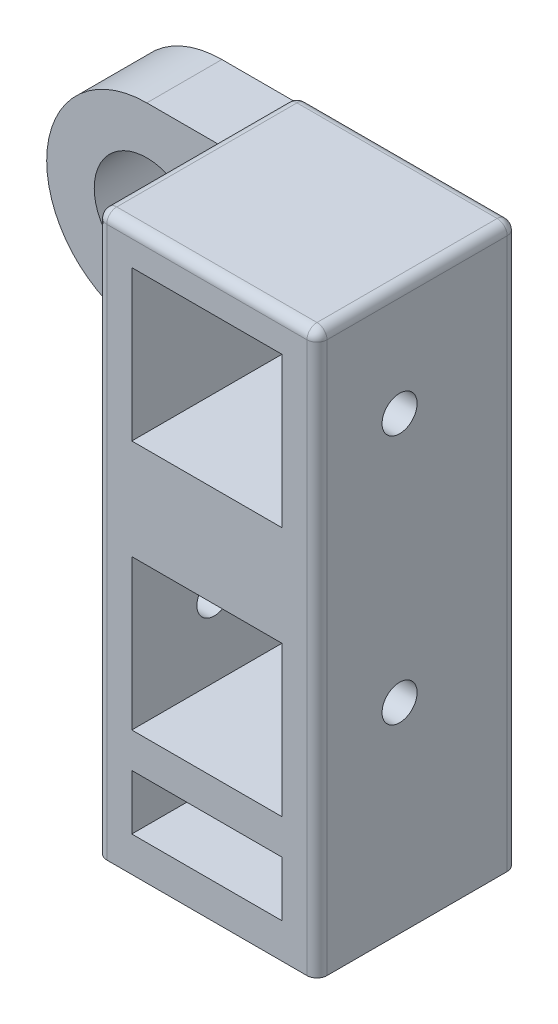
SolidWorks part; units mm, degrees
ref_plane "Front Plane" through (0, 0, 0) normal (0, 0, 1) x (1, 0, 0)
ref_plane "Top Plane" through (0, 0, 0) normal (0, 1, 0) x (1, 0, 0)
ref_plane "Right Plane" through (0, 0, 0) normal (1, 0, 0) x (0, 0, -1)
sketch "Sketch1" plane through (0, 0, 0) normal (0, 0, 1) x (1, 0, 0)
  line L1 (-25.0962, 42.3339) -> (-3.0962, 42.3339)
  line L2 (-25.0962, 42.3339) -> (-25.0962, -13.6661)
  line L3 (-25.0962, -13.6661) -> (-3.0962, -13.6661)
  line L4 (-3.0962, 42.3339) -> (-3.0962, -13.6661)
  line L5 (-21.5962, 38.8339) -> (-6.5962, 38.8339)
  line L6 (-21.5962, 38.8339) -> (-21.5962, 23.8339)
  line L7 (-21.5962, 23.8339) -> (-6.5962, 23.8339)
  line L8 (-6.5962, 38.8339) -> (-6.5962, 23.8339)
  dimension "D1" = 22
  dimension "D2" = 56
  dimension "D3" = 15
  dimension "D4" = 3.5
  dimension "D5" = 3.5
  dimension "D6" = 15
extrude "Boss-Extrude1" add sketch "Sketch1" along normal blind 20
sketch "Sketch2" plane through (0, 0, 20) normal (0, 0, 1) x (1, 0, 0)
  line L0 (-3.0962, -13.6661) -> (-3.0962, 42.3339) construction
  line L1 (-21.5962, 13.8339) -> (-6.5962, 13.8339)
  line L2 (-21.5962, 13.8339) -> (-21.5962, -1.1661)
  line L3 (-21.5962, -1.1661) -> (-6.5962, -1.1661)
  line L4 (-6.5962, 13.8339) -> (-6.5962, -1.1661)
  line L5 (-21.5962, 23.8339) -> (-6.5962, 23.8339) construction
  line L6 (-25.0962, -13.6661) -> (-3.0962, -13.6661) construction
  line L7 (-21.5962, -4.6661) -> (-6.5962, -4.6661)
  line L8 (-21.5962, -4.6661) -> (-21.5962, -10.1661)
  line L9 (-21.5962, -10.1661) -> (-6.5962, -10.1661)
  line L10 (-6.5962, -4.6661) -> (-6.5962, -10.1661)
  dimension "D1" = 15
  dimension "D2" = 3.5
  dimension "D3" = 10
  dimension "D4" = 15
  dimension "D5" = 15
  dimension "D6" = 3.5
  dimension "D7" = 3.5
extrude "Cut-Extrude1" cut sketch "Sketch2" against normal offset from surface (15.5 mm away) 4.5 up to face at (-14.0962, 14.3339, 0)
sketch "Sketch4" plane through (0, 0, 0) normal (0, 0, -1) x (-1, 0, 0)
  line L0 (21.5962, 31.3339) -> (55.1532, 31.3339) construction
  line L1 (21.5962, 38.8339) -> (21.5962, 23.8339) construction
  line L3 (32.5962, 41.3339) -> (25.0962, 41.3339)
  line L4 (25.0962, 42.3339) -> (25.0962, -13.6661) construction
  line L6 (25.0962, 41.3339) -> (25.0962, 21.3339)
  line L7 (25.0962, 21.3339) -> (32.5962, 21.3339)
  circle A0 centre (32.5962, 31.3339) radius 5.25
  arc A1 (32.5962, 21.3339) -> (32.5962, 41.3339) centre (32.5962, 31.3339) ccw
  dimension "D1" = 10.5
  dimension "D2" = 20
  dimension "D3" = 7.5
extrude "Boss-Extrude3" add sketch "Sketch4" against normal blind 7.5
fillet "Fillet4" radius 1 8 edges at (-3.0962, 14.3339, 20) (-25.0962, 14.3339, 20) (-14.0962, 42.3339, 20) (-3.0962, 42.3339, 10) (-14.0962, 42.3339, 0) (-25.0962, 42.3339, 10) (-3.0962, 14.3339, 0)
sketch "Sketch5" plane through (-3.0962, 0, 0) normal (1, 0, 0) x (0, 0, -1)
  line L0 (-11.75, -13.6661) -> (-11.75, 44.1049) construction
  line L1 (-19, -13.6661) -> (-1, -13.6661) construction
  line L2 (-20, -13.6661) -> (-20, 41.3339) construction
  line L3 (-20, 38.8339) -> (0, 38.8339) construction
  line L4 (-4.5, -1.1661) -> (-20, -1.1661) construction
  circle A0 centre (-11.75, 31.3339) radius 1.75
  circle A1 centre (-11.75, 6.3339) radius 1.75
  dimension "D2" = 3.5
  dimension "D3" = 7.5
  dimension "D4" = 7.5
  dimension "D1" = 8.25
extrude "Cut-Extrude2" cut sketch "Sketch5" against normal blind 10
sketch "Sketch6" plane through (-25.0962, 0, 0) normal (-1, 0, 0) x (0, 0, 1)
  circle A0 centre (11.75, 6.3339) radius 1.75
extrude "Cut-Extrude3" cut sketch "Sketch6" against normal blind 10
